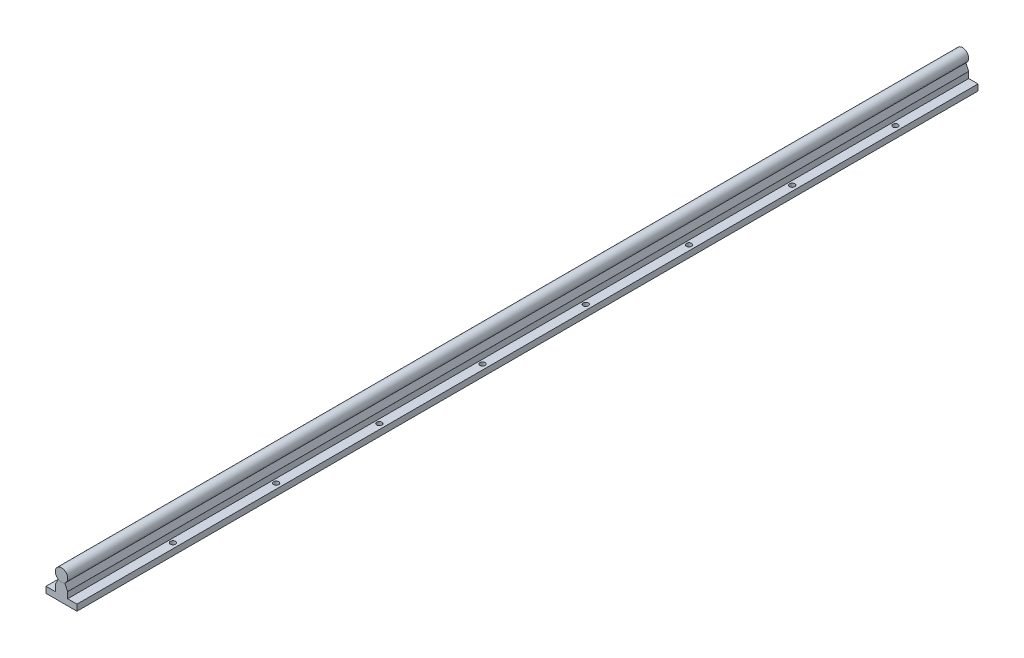
SolidWorks part; units mm, degrees
material "AISI 1045 Steel, cold drawn"
ref_plane "Front Plane" through (0, 0, 0) normal (0, 0, 1) x (1, 0, 0)
ref_plane "Top Plane" through (0, 0, 0) normal (0, 1, 0) x (1, 0, 0)
ref_plane "Right Plane" through (0, 0, 0) normal (1, 0, 0) x (0, 0, -1)
sketch "SBS-Profile" plane through (0, 0, 0) normal (0, 0, 1) x (1, 0, 0)
  line L0 (0, 0) -> (0, -23) construction
  line L2 (-15, -23) -> (15, -23)
  line L3 (-15, -23) -> (-15, -17)
  line L4 (-15, -17) -> (-6, -17)
  line L5 (15, -23) -> (15, -17)
  line L6 (-6, -11) -> (-6, -17)
  line L8 (6, -11) -> (6, -17)
  line L9 (6, -17) -> (15, -17)
  line L10 (-6, -11) -> (-5.9627, -11)
  line L11 (-5.9627, -11) -> (-3.2, -5.0754)
  line L12 (6, -11) -> (5.9627, -11)
  line L13 (5.9627, -11) -> (3.2, -5.0754)
  circle A0 centre (0, 0) radius 6
  dimension "D" = 12
  dimension "B" = 30
  dimension "T" = 6
  dimension "G" = 12
  dimension "F" = 12
  dimension "h" = 23
  dimension "Theta" = 50
  dimension "X" = 6.4
extrude "SteelRail" add sketch "SBS-Profile" along normal blind 873 contours A0
extrude "AluminumSupport" add sketch "SBS-Profile<3>" along normal up to surface (873 mm away) separate body contours A0 L0 L2 L5 L9 L8 | L0 A0 L6 L4 L3 L2 region at (5.5885, -16.6691, 0) region at (-5.5885, -16.6691, 0) up to face at (6, 0, 873)
sketch "SBS-Profile<3>" plane through (0, 0, 0) normal (0, 0, 1) x (1, 0, 0) same geometry as "SBS-Profile"
hole_wizard "MountHoles" positions "HolePos" profile "HoleDia" hole size "Ø5.0" standard "DIN" end condition up to next
sketch "HolePos" plane through (0, -23, 0) normal (0, -1, 0) x (-1, 0, 0)
  line L0 (0, 0) -> (0, -75) construction
  line L1 (15, 0) -> (-15, 0) construction
  point P0 (-10, -75)
  point P2 (10, -75)
  dimension "N" = 75
  dimension "C" = 20
sketch "HoleDia" plane through (10, -23, 75) normal (1, 0, 0) x (0, 0, -1)
  line L0 (0, 0) -> (0, 6.001)
  line L1 (0, 6.001) -> (2.5, 6.001)
  line L2 (2.5, 6.001) -> (2.5, 0)
  line L5 (2.5, 0) -> (0, 0)
  line L11 (0, -6.35) -> (0, 107.95) construction
  dimension "Thru Hole Dia." = 5
  dimension "Thru Hole Depth" = 6.001
pattern_linear "LPattern1" count 8 spacing 100 along (0, 0, 1) of "MountHoles"
